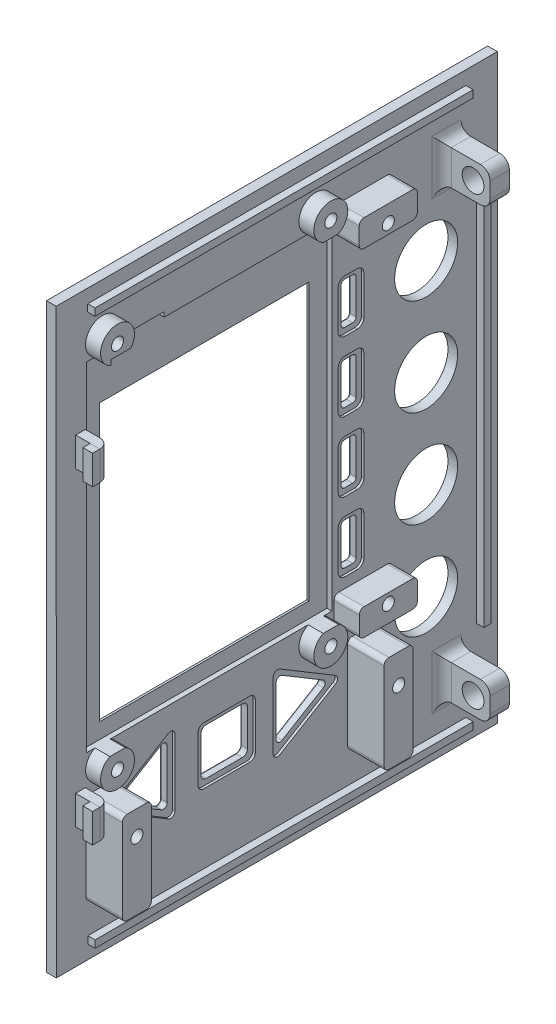
SolidWorks part; units mm, degrees
ref_plane "Front Plane" through (0, 0, 0) normal (0, 0, 1) x (1, 0, 0)
ref_plane "Top Plane" through (0, 0, 0) normal (0, 1, 0) x (1, 0, 0)
ref_plane "Right Plane" through (0, 0, 0) normal (1, 0, 0) x (0, 0, -1)
ref_plane "Plane2" through (-1175.548, -0.0877, 0) normal (-1, -0.0001, 0) x (0, 0, 1)
sketch "Sketch2" plane through (-1175.548, -0.0877, 0) normal (-1, -0.0001, 0) x (0, 0, 1)
  line L0 (-1289.195, -889.282) -> (-1289.195, -789.282) construction
  line L1 (-1204.195, -779.282) -> (-1295.195, -779.282)
  line L2 (-1204.195, -779.282) -> (-1204.195, -899.282)
  line L3 (-1204.195, -899.282) -> (-1295.195, -899.282)
  line L4 (-1295.195, -779.282) -> (-1295.195, -899.282)
  line L5 (-1289.195, -889.282) -> (-1287.685, -889.282) construction
  line L6 (-1289.195, -789.282) -> (-1287.685, -789.282) construction
  circle A0 centre (-1280.5, -869.282) radius 6.5
  circle A1 centre (-1280.5, -849.282) radius 6.5
  circle A2 centre (-1280.5, -829.282) radius 6.5
  circle A3 centre (-1280.5, -809.282) radius 6.5
  ellipse E0 centre (-1280.5, -869.282) end of major axis (-1281.15, -869.2796) minor radius 0.65 construction
  ellipse E1 centre (-1280.5, -849.282) end of major axis (-1281.15, -849.2796) minor radius 0.65 construction
  ellipse E2 centre (-1280.5, -829.282) end of major axis (-1281.15, -829.2796) minor radius 0.65 construction
  ellipse E3 centre (-1280.5, -809.282) end of major axis (-1281.15, -809.2796) minor radius 0.65 construction
  ellipse E4 centre (-1280.5, -869.282) end of major axis (-1281.15, -869.2796) minor radius 0.65
  ellipse E5 centre (-1280.5, -849.282) end of major axis (-1281.15, -849.2796) minor radius 0.65 construction
  ellipse E6 centre (-1280.5, -829.282) end of major axis (-1281.15, -829.2796) minor radius 0.65
  ellipse E7 centre (-1280.5, -809.282) end of major axis (-1281.15, -809.2796) minor radius 0.65
  dimension "D5" = 13
  dimension "D6" = 13
  dimension "D7" = 13
  dimension "D8" = 13
  dimension "D1" = 6
  dimension "D2" = 10
  dimension "D3" = 10
  dimension "D4" = 91
extrude "Boss-Extrude2" add sketch "Sketch2" along normal blind 2 contours L1 L4 L3 L2 A3 A2 A1 A0 region at (-1175.4854, -839.3697, -1248.1207)
sketch "Sketch3" plane through (-1177.548, -0.0879, 0) normal (-1, -0.0001, 0) x (0, 0, 1)
  line L12 (-1214.15, -858.982) -> (-1257.35, -858.982) construction
  line L13 (-1257.35, -858.982) -> (-1257.35, -802.002) construction
  line L14 (-1214.15, -802.002) -> (-1214.15, -858.982) construction
  line L15 (-1257.35, -802.002) -> (-1214.15, -802.002) construction
  line L16 (-1214.15, -858.982) -> (-1257.35, -858.982)
  line L17 (-1257.35, -858.982) -> (-1257.35, -802.002)
  line L18 (-1214.15, -802.002) -> (-1214.15, -858.982)
  line L19 (-1257.35, -802.002) -> (-1214.15, -802.002)
extrude "tft_cutout" cut sketch "Sketch3" against normal through all
sketch "tft_inset_cutout" plane through (-1175.548, -0.0877, 0) normal (1, 0.0001, 0) x (0, 0, -1)
  line L4 (1210.95, -792.861) -> (1210.95, -861.661) construction
  line L5 (1260.55, -792.861) -> (1210.95, -792.861) construction
  line L12 (1260.55, -861.661) -> (1260.55, -792.861) construction
  line L17 (1210.95, -861.661) -> (1260.55, -861.661) construction
  line L18 (1260.55, -861.661) -> (1260.55, -792.861) construction
  line L19 (1210.95, -861.661) -> (1260.55, -861.661) construction
  line L20 (1210.95, -792.861) -> (1210.95, -861.661) construction
  line L21 (1260.55, -792.861) -> (1210.95, -792.861) construction
  line L22 (1261.05, -792.361) -> (1210.45, -792.361)
  line L26 (1212.45, -792.861) -> (1226.45, -792.861)
  line L27 (1212.45, -792.861) -> (1212.45, -791.361)
  line L28 (1212.45, -791.361) -> (1226.45, -791.361)
  line L29 (1226.45, -792.861) -> (1226.45, -791.361)
  line L30 (1210.45, -792.361) -> (1210.45, -862.161)
  line L31 (1210.45, -862.161) -> (1261.05, -862.161)
  line L32 (1261.05, -862.161) -> (1261.05, -792.361)
  line M40 (1257.35, -858.982) -> (1214.15, -858.982)
  line M41 (1214.15, -858.982) -> (1214.15, -802.002)
  line M42 (1214.15, -802.002) -> (1257.35, -802.002)
  line M43 (1257.35, -802.002) -> (1257.35, -858.982)
  dimension "D3" = 1.5
  dimension "D4" = 0.5
  dimension "D1" = 14
  dimension "D2" = 1.5
extrude "Cut-Extrude2" cut sketch "tft_inset_cutout" against normal up to surface (1 mm away) contours L18 | L31 L32 L22 L29 L26 L27 L30 M43 M40 M41 M42 | L26 L29 L22 L27 | L22 L29 L28 L27 region at (-1175.4863, -827.3487, -1260.1879) region at (-1175.4889, -792.6987, -1219.45) region at (-1175.4889, -791.9487, -1219.45)
chamfer "Chamfer2" distance 1 angle 30 4 edges at (-1177.486, -830.5799, -1257.35) (-1177.4839, -859.0699, -1235.75) (-1177.486, -830.5799, -1214.15) (-1177.4882, -802.0899, -1235.75) first distance on face at (-1177.486, -830.5799, -1235.75)
sketch "Sketch6" plane through (-1175.548, -0.0877, 0) normal (1, 0.0001, 0) x (0, 0, -1)
  line L5 (1261.5, -864.9905) -> (1273.5, -864.9905)
  line L6 (1261.5, -864.9905) -> (1261.5, -859.4905)
  line L7 (1261.5, -859.4905) -> (1273.5, -859.4905)
  line L8 (1261.5, -864.9905) -> (1273.5, -864.9905)
  line L9 (1273.5, -864.9905) -> (1273.5, -789.9905)
  line L10 (1273.5, -789.9905) -> (1261.5, -789.9905)
  line L11 (1261.5, -789.9905) -> (1261.5, -864.9905)
  line L12 (1261.5, -864.9905) -> (1273.5, -864.9905) construction
  line L13 (1273.5, -864.9905) -> (1273.5, -789.9905) construction
  line L14 (1273.5, -789.9905) -> (1261.5, -789.9905) construction
  line L15 (1261.5, -789.9905) -> (1261.5, -864.9905) construction
  line L16 (1273.5, -864.9905) -> (1273.5, -859.4905)
  line L17 (1261.5, -789.9905) -> (1273.5, -789.9905)
  line L18 (1261.5, -789.9905) -> (1261.5, -795.4905)
  line L19 (1261.5, -795.4905) -> (1273.5, -795.4905)
  line L20 (1273.5, -789.9905) -> (1273.5, -795.4905)
  circle A0 centre (1267.5, -861.4905) radius 1.25 construction
  circle A1 centre (1267.5, -861.4905) radius 1.25 construction
  circle A2 centre (1267.5, -861.4905) radius 1.25
  circle A3 centre (1267.5, -793.4905) radius 1.25 construction
  circle A4 centre (1267.5, -793.4905) radius 1.25 construction
  circle A5 centre (1267.5, -793.4905) radius 1.25
  dimension "D2" = 2.5
  dimension "D4" = 2.5
  dimension "D3" = 2
  dimension "D5" = 2
extrude "menu_standoffs" add sketch "Sketch6" along normal up to surface (5.203 mm away)
fillet "Fillet1" radius 1 8 edges at (-1172.8871, -795.5781, -1261.5) (-1172.8871, -795.5781, -1273.5) (-1172.8875, -790.0781, -1273.5) (-1172.8875, -790.0781, -1261.5) (-1172.8824, -859.5781, -1273.5) (-1172.8824, -859.5781, -1261.5) (-1172.882, -865.0781, -1261.5) (-1172.882, -865.0781, -1273.5)
sketch "Sketch7" plane through (-1170.345, -0.0874, 0) normal (1, 0.0001, 0) x (0, 0, -1)
  circle A0 centre (1267.5, -861.4905) radius 1.25 construction
  circle A1 centre (1267.5, -793.4905) radius 1.25 construction
  circle A2 centre (1267.5, -861.4905) radius 1.25
  circle A3 centre (1267.5, -793.4905) radius 1.25
extrude "menu_standoff_holes" [suppressed] cut sketch "Sketch7" against normal blind 5 contours A2
sketch "Sketch8" plane through (-1175.548, -0.0877, 0) normal (1, 0.0001, 0) x (0, 0, -1)
  circle A0 centre (1213.75, -865.282) radius 1.55 construction
  circle A1 centre (1257.75, -865.282) radius 1.55 construction
  circle A2 centre (1257.75, -789.202) radius 1.55 construction
  circle A3 centre (1213.75, -789.2023) radius 1.55 construction
  circle A4 centre (1213.75, -865.282) radius 1.55 construction
  circle A5 centre (1257.75, -865.282) radius 1.55 construction
  circle A6 centre (1257.75, -789.202) radius 1.55 construction
  circle A7 centre (1213.75, -789.2023) radius 1.55 construction
  circle A8 centre (1213.75, -789.2023) radius 3.5
  circle A9 centre (1257.75, -789.202) radius 3.5
  circle A10 centre (1257.75, -865.282) radius 3.5
  circle A11 centre (1213.75, -865.282) radius 3.5
  circle A12 centre (1213.75, -789.2023) radius 1.25
  circle A13 centre (1213.75, -865.282) radius 1.25
  circle A14 centre (1257.75, -865.282) radius 1.25
  circle A15 centre (1257.75, -789.202) radius 1.25
  dimension "D2" = 2.5
  dimension "D1" = 7
extrude "TFT_standoffs" add sketch "Sketch8" along normal up to surface (3.09 mm away)
sketch "Sketch9" plane through (-1175.548, -0.0877, 0) normal (1, 0.0001, 0) x (0, 0, -1)
  circle A0 centre (1213.75, -789.2023) radius 1.25 construction
  circle A1 centre (1213.75, -865.282) radius 1.25 construction
  circle A2 centre (1257.75, -865.282) radius 1.25 construction
  circle A3 centre (1257.75, -789.202) radius 1.25 construction
  circle A4 centre (1213.75, -789.2023) radius 1.25
  circle A5 centre (1213.75, -865.282) radius 1.25
  circle A6 centre (1257.75, -865.282) radius 1.25
  circle A7 centre (1257.75, -789.202) radius 1.25
extrude "TFT_standoff_holes" cut sketch "Sketch9" against normal offset from surface (1 mm away) 1 up to face at (-1177.486, -830.5799, -1235.75)
extrude "Cut-Extrude5" cut sketch "Sketch5<3>" along normal through all contours L31 L32 L22 L29 L26 L27 L30 M43 M40 M41 M42 | L22 L29 L28 L27 | L26 L29 L22 L27 region at (-1175.4863, -827.3487, -1260.1879) region at (-1175.4889, -792.6987, -1219.45) region at (-1175.4889, -791.9487, -1219.45)
sketch "Sketch5<3>" plane through (-1175.548, -0.0877, 0) normal (1, 0.0001, 0) x (0, 0, -1) same geometry as "tft_inset_cutout"
sketch "Sketch10" plane through (-1175.548, -0.0877, 0) normal (1, 0.0001, 0) x (0, 0, -1)
  line L0 (1267.2535, -804.997) -> (1267.2535, -812.997) construction
  line L1 (1266.2535, -813.997) -> (1263.7535, -813.997) construction
  line L2 (1262.7535, -812.997) -> (1262.7535, -804.997) construction
  line L3 (1263.7535, -803.997) -> (1266.2535, -803.997) construction
  line L4 (1267.2535, -804.997) -> (1267.2535, -812.997) construction
  line L5 (1266.2535, -813.997) -> (1263.7535, -813.997) construction
  line L6 (1262.7535, -812.997) -> (1262.7535, -804.997) construction
  line L7 (1263.7535, -803.997) -> (1266.2535, -803.997) construction
  line L8 (1267.6535, -804.997) -> (1267.6535, -812.997)
  line L9 (1266.2535, -814.397) -> (1263.7535, -814.397)
  line L10 (1262.3535, -812.997) -> (1262.3535, -804.997)
  line L11 (1263.7535, -803.597) -> (1266.2535, -803.597)
  line L12 (1267.6535, -819.327) -> (1267.6535, -827.327)
  line L13 (1266.2535, -828.727) -> (1263.7535, -828.727)
  line L14 (1262.3535, -827.327) -> (1262.3535, -819.327)
  line L15 (1263.7535, -817.927) -> (1266.2535, -817.927)
  line L16 (1267.2535, -819.327) -> (1267.2535, -827.327) construction
  line L17 (1266.2535, -828.327) -> (1263.7535, -828.327) construction
  line L18 (1262.7535, -827.327) -> (1262.7535, -819.327) construction
  line L19 (1263.7535, -818.327) -> (1266.2535, -818.327) construction
  line L20 (1267.6535, -833.657) -> (1267.6535, -841.657)
  line L21 (1266.2535, -843.057) -> (1263.7535, -843.057)
  line L22 (1262.3535, -841.657) -> (1262.3535, -833.657)
  line L23 (1263.7535, -832.257) -> (1266.2535, -832.257)
  line L24 (1267.2535, -833.657) -> (1267.2535, -841.657) construction
  line L25 (1266.2535, -842.657) -> (1263.7535, -842.657) construction
  line L26 (1262.7535, -841.657) -> (1262.7535, -833.657) construction
  line L27 (1263.7535, -832.657) -> (1266.2535, -832.657) construction
  line L28 (1267.6535, -847.987) -> (1267.6535, -855.987)
  line L29 (1266.2535, -857.387) -> (1263.7535, -857.387)
  line L30 (1262.3535, -855.987) -> (1262.3535, -847.987)
  line L31 (1263.7535, -846.587) -> (1266.2535, -846.587)
  line L32 (1267.2535, -847.987) -> (1267.2535, -855.987) construction
  line L33 (1266.2535, -856.987) -> (1263.7535, -856.987) construction
  line L34 (1262.7535, -855.987) -> (1262.7535, -847.987) construction
  line L35 (1263.7535, -846.987) -> (1266.2535, -846.987) construction
  arc A0 (1267.2535, -804.997) -> (1266.2535, -803.997) centre (1266.2535, -804.997) ccw construction
  arc A1 (1266.2535, -813.997) -> (1267.2535, -812.997) centre (1266.2535, -812.997) ccw construction
  arc A2 (1262.7535, -812.997) -> (1263.7535, -813.997) centre (1263.7535, -812.997) ccw construction
  arc A3 (1263.7535, -803.997) -> (1262.7535, -804.997) centre (1263.7535, -804.997) ccw construction
  arc A4 (1267.2535, -804.997) -> (1266.2535, -803.997) centre (1266.2535, -804.997) ccw construction
  arc A5 (1266.2535, -813.997) -> (1267.2535, -812.997) centre (1266.2535, -812.997) ccw construction
  arc A6 (1262.7535, -812.997) -> (1263.7535, -813.997) centre (1263.7535, -812.997) ccw construction
  arc A7 (1263.7535, -803.997) -> (1262.7535, -804.997) centre (1263.7535, -804.997) ccw construction
  arc A8 (1266.2535, -814.397) -> (1267.6535, -812.997) centre (1266.2535, -812.997) ccw
  arc A9 (1262.3535, -812.997) -> (1263.7535, -814.397) centre (1263.7535, -812.997) ccw
  arc A10 (1263.7535, -803.597) -> (1262.3535, -804.997) centre (1263.7535, -804.997) ccw
  arc A11 (1267.6535, -804.997) -> (1266.2535, -803.597) centre (1266.2535, -804.997) ccw
  arc A12 (1266.2535, -828.727) -> (1267.6535, -827.327) centre (1266.2535, -827.327) ccw
  arc A13 (1262.3535, -827.327) -> (1263.7535, -828.727) centre (1263.7535, -827.327) ccw
  arc A14 (1263.7535, -817.927) -> (1262.3535, -819.327) centre (1263.7535, -819.327) ccw
  arc A15 (1267.6535, -819.327) -> (1266.2535, -817.927) centre (1266.2535, -819.327) ccw
  arc A16 (1267.2535, -819.327) -> (1266.2535, -818.327) centre (1266.2535, -819.327) ccw construction
  arc A17 (1266.2535, -828.327) -> (1267.2535, -827.327) centre (1266.2535, -827.327) ccw construction
  arc A18 (1262.7535, -827.327) -> (1263.7535, -828.327) centre (1263.7535, -827.327) ccw construction
  arc A19 (1263.7535, -818.327) -> (1262.7535, -819.327) centre (1263.7535, -819.327) ccw construction
  arc A20 (1266.2535, -843.057) -> (1267.6535, -841.657) centre (1266.2535, -841.657) ccw
  arc A21 (1262.3535, -841.657) -> (1263.7535, -843.057) centre (1263.7535, -841.657) ccw
  arc A22 (1263.7535, -832.257) -> (1262.3535, -833.657) centre (1263.7535, -833.657) ccw
  arc A23 (1267.6535, -833.657) -> (1266.2535, -832.257) centre (1266.2535, -833.657) ccw
  arc A24 (1267.2535, -833.657) -> (1266.2535, -832.657) centre (1266.2535, -833.657) ccw construction
  arc A25 (1266.2535, -842.657) -> (1267.2535, -841.657) centre (1266.2535, -841.657) ccw construction
  arc A26 (1262.7535, -841.657) -> (1263.7535, -842.657) centre (1263.7535, -841.657) ccw construction
  arc A27 (1263.7535, -832.657) -> (1262.7535, -833.657) centre (1263.7535, -833.657) ccw construction
  arc A28 (1266.2535, -857.387) -> (1267.6535, -855.987) centre (1266.2535, -855.987) ccw
  arc A29 (1262.3535, -855.987) -> (1263.7535, -857.387) centre (1263.7535, -855.987) ccw
  arc A30 (1263.7535, -846.587) -> (1262.3535, -847.987) centre (1263.7535, -847.987) ccw
  arc A31 (1267.6535, -847.987) -> (1266.2535, -846.587) centre (1266.2535, -847.987) ccw
  arc A32 (1267.2535, -847.987) -> (1266.2535, -846.987) centre (1266.2535, -847.987) ccw construction
  arc A33 (1266.2535, -856.987) -> (1267.2535, -855.987) centre (1266.2535, -855.987) ccw construction
  arc A34 (1262.7535, -855.987) -> (1263.7535, -856.987) centre (1263.7535, -855.987) ccw construction
  arc A35 (1263.7535, -846.987) -> (1262.7535, -847.987) centre (1263.7535, -847.987) ccw construction
  dimension "D1" = 0.4
  dimension "D2" = 4
extrude "menu_panel_inset" cut sketch "Sketch10" against normal offset from surface 1.5 and the other way through all up to face at (-1177.486, -830.5799, -1235.75)
sketch "Sketch11" plane through (-1177.548, -0.0879, 0) normal (-1, -0.0001, 0) x (0, 0, 1)
  line L0 (-1265.8535, -812.997) -> (-1264.1535, -812.997) construction
  line L1 (-1266.2535, -805.397) -> (-1266.2535, -812.597) construction
  line L2 (-1265.8535, -804.997) -> (-1264.1535, -804.997) construction
  line L3 (-1263.7535, -805.397) -> (-1263.7535, -812.597) construction
  line L4 (-1265.8535, -812.997) -> (-1264.1535, -812.997) construction
  line L5 (-1266.2535, -805.397) -> (-1266.2535, -812.597) construction
  line L6 (-1265.8535, -804.997) -> (-1264.1535, -804.997) construction
  line L7 (-1263.7535, -805.397) -> (-1263.7535, -812.597) construction
  line L8 (-1263.4535, -805.397) -> (-1263.4535, -812.597)
  line L9 (-1265.8535, -813.297) -> (-1264.1535, -813.297)
  line L10 (-1266.5535, -805.397) -> (-1266.5535, -812.597)
  line L11 (-1265.8535, -804.697) -> (-1264.1535, -804.697)
  line L12 (-1263.4535, -819.727) -> (-1263.4535, -826.927)
  line L13 (-1265.8535, -827.627) -> (-1264.1535, -827.627)
  line L14 (-1266.5535, -819.727) -> (-1266.5535, -826.927)
  line L15 (-1265.8535, -819.027) -> (-1264.1535, -819.027)
  line L16 (-1265.8535, -827.327) -> (-1264.1535, -827.327) construction
  line L17 (-1266.2535, -819.727) -> (-1266.2535, -826.927) construction
  line L18 (-1265.8535, -819.327) -> (-1264.1535, -819.327) construction
  line L19 (-1263.7535, -819.727) -> (-1263.7535, -826.927) construction
  line L20 (-1263.4535, -834.057) -> (-1263.4535, -841.257)
  line L21 (-1265.8535, -841.957) -> (-1264.1535, -841.957)
  line L22 (-1266.5535, -834.057) -> (-1266.5535, -841.257)
  line L23 (-1265.8535, -833.357) -> (-1264.1535, -833.357)
  line L24 (-1265.8535, -841.657) -> (-1264.1535, -841.657) construction
  line L25 (-1266.2535, -834.057) -> (-1266.2535, -841.257) construction
  line L26 (-1265.8535, -833.657) -> (-1264.1535, -833.657) construction
  line L27 (-1263.7535, -834.057) -> (-1263.7535, -841.257) construction
  line L28 (-1263.4535, -848.387) -> (-1263.4535, -855.587)
  line L29 (-1265.8535, -856.287) -> (-1264.1535, -856.287)
  line L30 (-1266.5535, -848.387) -> (-1266.5535, -855.587)
  line L31 (-1265.8535, -847.687) -> (-1264.1535, -847.687)
  line L32 (-1265.8535, -855.987) -> (-1264.1535, -855.987) construction
  line L33 (-1266.2535, -848.387) -> (-1266.2535, -855.587) construction
  line L34 (-1265.8535, -847.987) -> (-1264.1535, -847.987) construction
  line L35 (-1263.7535, -848.387) -> (-1263.7535, -855.587) construction
  arc A0 (-1264.1535, -812.997) -> (-1263.7535, -812.597) centre (-1264.1535, -812.597) ccw construction
  arc A1 (-1266.2535, -812.597) -> (-1265.8535, -812.997) centre (-1265.8535, -812.597) ccw construction
  arc A2 (-1265.8535, -804.997) -> (-1266.2535, -805.397) centre (-1265.8535, -805.397) ccw construction
  arc A3 (-1263.7535, -805.397) -> (-1264.1535, -804.997) centre (-1264.1535, -805.397) ccw construction
  arc A4 (-1264.1535, -812.997) -> (-1263.7535, -812.597) centre (-1264.1535, -812.597) ccw construction
  arc A5 (-1266.2535, -812.597) -> (-1265.8535, -812.997) centre (-1265.8535, -812.597) ccw construction
  arc A6 (-1265.8535, -804.997) -> (-1266.2535, -805.397) centre (-1265.8535, -805.397) ccw construction
  arc A7 (-1263.7535, -805.397) -> (-1264.1535, -804.997) centre (-1264.1535, -805.397) ccw construction
  arc A8 (-1264.1535, -813.297) -> (-1263.4535, -812.597) centre (-1264.1535, -812.597) ccw
  arc A9 (-1266.5535, -812.597) -> (-1265.8535, -813.297) centre (-1265.8535, -812.597) ccw
  arc A10 (-1265.8535, -804.697) -> (-1266.5535, -805.397) centre (-1265.8535, -805.397) ccw
  arc A11 (-1263.4535, -805.397) -> (-1264.1535, -804.697) centre (-1264.1535, -805.397) ccw
  arc A12 (-1264.1535, -827.627) -> (-1263.4535, -826.927) centre (-1264.1535, -826.927) ccw
  arc A13 (-1266.5535, -826.927) -> (-1265.8535, -827.627) centre (-1265.8535, -826.927) ccw
  arc A14 (-1265.8535, -819.027) -> (-1266.5535, -819.727) centre (-1265.8535, -819.727) ccw
  arc A15 (-1263.4535, -819.727) -> (-1264.1535, -819.027) centre (-1264.1535, -819.727) ccw
  arc A16 (-1264.1535, -827.327) -> (-1263.7535, -826.927) centre (-1264.1535, -826.927) ccw construction
  arc A17 (-1266.2535, -826.927) -> (-1265.8535, -827.327) centre (-1265.8535, -826.927) ccw construction
  arc A18 (-1265.8535, -819.327) -> (-1266.2535, -819.727) centre (-1265.8535, -819.727) ccw construction
  arc A19 (-1263.7535, -819.727) -> (-1264.1535, -819.327) centre (-1264.1535, -819.727) ccw construction
  arc A20 (-1264.1535, -841.957) -> (-1263.4535, -841.257) centre (-1264.1535, -841.257) ccw
  arc A21 (-1266.5535, -841.257) -> (-1265.8535, -841.957) centre (-1265.8535, -841.257) ccw
  arc A22 (-1265.8535, -833.357) -> (-1266.5535, -834.057) centre (-1265.8535, -834.057) ccw
  arc A23 (-1263.4535, -834.057) -> (-1264.1535, -833.357) centre (-1264.1535, -834.057) ccw
  arc A24 (-1264.1535, -841.657) -> (-1263.7535, -841.257) centre (-1264.1535, -841.257) ccw construction
  arc A25 (-1266.2535, -841.257) -> (-1265.8535, -841.657) centre (-1265.8535, -841.257) ccw construction
  arc A26 (-1265.8535, -833.657) -> (-1266.2535, -834.057) centre (-1265.8535, -834.057) ccw construction
  arc A27 (-1263.7535, -834.057) -> (-1264.1535, -833.657) centre (-1264.1535, -834.057) ccw construction
  arc A28 (-1264.1535, -856.287) -> (-1263.4535, -855.587) centre (-1264.1535, -855.587) ccw
  arc A29 (-1266.5535, -855.587) -> (-1265.8535, -856.287) centre (-1265.8535, -855.587) ccw
  arc A30 (-1265.8535, -847.687) -> (-1266.5535, -848.387) centre (-1265.8535, -848.387) ccw
  arc A31 (-1263.4535, -848.387) -> (-1264.1535, -847.687) centre (-1264.1535, -848.387) ccw
  arc A32 (-1264.1535, -855.987) -> (-1263.7535, -855.587) centre (-1264.1535, -855.587) ccw construction
  arc A33 (-1266.2535, -855.587) -> (-1265.8535, -855.987) centre (-1265.8535, -855.587) ccw construction
  arc A34 (-1265.8535, -847.987) -> (-1266.2535, -848.387) centre (-1265.8535, -848.387) ccw construction
  arc A35 (-1263.7535, -848.387) -> (-1264.1535, -847.987) centre (-1264.1535, -848.387) ccw construction
  dimension "D1" = 0.3
  dimension "D2" = 4
extrude "menu_panel_cutout" cut sketch "Sketch11" against normal through all
fillet "Fillet2" radius 0.25 32 edges at (-1177.4876, -809.0849, -1263.4535) (-1177.4873, -813.1798, -1263.6586) (-1177.4873, -813.3849, -1265.0035) (-1177.4873, -813.1798, -1266.3485) (-1177.4876, -809.0849, -1266.5535) (-1177.4879, -804.9899, -1266.3485) (-1177.488, -804.7849, -1265.0035) (-1177.4862, -827.7149, -1265.0035) (-1177.4863, -827.5098, -1266.3485) (-1177.4866, -823.4149, -1266.5535) (-1177.4869, -819.3199, -1266.3485) (-1177.4869, -819.1149, -1265.0035) (-1177.4869, -819.3199, -1263.6586) (-1177.4866, -823.4149, -1263.4535) (-1177.4852, -842.0449, -1265.0035) (-1177.4852, -841.8398, -1266.3485) (-1177.4855, -837.7449, -1266.5535) (-1177.4858, -833.6499, -1266.3485) (-1177.4858, -833.4449, -1265.0035) (-1177.4858, -833.6499, -1263.6586) (-1177.4855, -837.7449, -1263.4535) (-1177.4844, -852.0749, -1263.4535) (-1177.4841, -856.1698, -1263.6586) (-1177.4841, -856.3749, -1265.0035) (-1177.4841, -856.1698, -1266.3485) (-1177.4844, -852.0749, -1266.5535) (-1177.4847, -847.9799, -1266.3485) (-1177.4847, -847.7749, -1265.0035) (-1177.4879, -804.9899, -1263.6586) (-1177.4863, -827.5098, -1263.6586) (-1177.4852, -841.8398, -1263.6586) (-1177.4847, -847.9799, -1263.6586)
sketch "Sketch12" plane through (-1175.548, -0.0877, 0) normal (1, 0.0001, 0) x (0, 0, -1)
  line L0 (1270.2797, -888.782) -> (1210.2797, -888.782) construction
  line L1 (1270.2797, -868.782) -> (1264.2797, -868.782)
  line L2 (1270.2797, -868.782) -> (1270.2797, -888.782)
  line L3 (1270.2797, -888.782) -> (1264.2797, -888.782)
  line L4 (1264.2797, -868.782) -> (1264.2797, -888.782)
  line L6 (1210.2797, -888.782) -> (1216.2797, -888.782)
  line L7 (1210.2797, -888.782) -> (1210.2797, -869.782)
  line L8 (1210.2797, -869.782) -> (1216.2797, -869.782)
  line L9 (1216.2797, -888.782) -> (1216.2797, -869.782)
  line L10 (1210.2797, -868.782) -> (1270.2797, -868.782) construction
  circle A0 centre (1267.2797, -874.782) radius 1.25
  circle A1 centre (1213.2797, -874.782) radius 1.25
  dimension "D1" = 6
  dimension "D2" = 2.5
  dimension "D4" = 2.5
  dimension "D3" = 6
  dimension "D5" = 1
extrude "selector_standoffs" add sketch "Sketch12" along normal up to surface (7.55 mm away) contours L6 L9 L8 L7 A1 | L1 L4 L3 L2 A0 region at (-1175.4824, -879.0403, -1267.2797) region at (-1175.4824, -879.5722, -1213.2797)
fillet "Fillet3" radius 1 8 edges at (-1171.7067, -888.8694, -1270.2797) (-1171.7082, -868.8694, -1270.2797) (-1171.7082, -868.8694, -1264.2797) (-1171.7067, -888.8694, -1264.2797) (-1171.7067, -888.8694, -1216.2797) (-1171.7067, -888.8694, -1210.2797) (-1171.7081, -869.8694, -1210.2797) (-1171.7081, -869.8694, -1216.2797)
sketch "Sketch13" plane through (-1175.548, -0.0877, 0) normal (1, 0.0001, 0) x (0, 0, -1)
  line L0 (1218.0014, -875.2178) -> (1226.5296, -880.3347) construction
  line L1 (1227.2868, -879.906) -> (1227.2868, -869.6722) construction
  line L2 (1226.5296, -869.2434) -> (1218.0014, -874.3603) construction
  line L3 (1234.85, -871.0391) -> (1234.85, -878.5391) construction
  line L4 (1235.6, -879.2891) -> (1243.1, -879.2891) construction
  line L5 (1243.1, -870.2891) -> (1235.6, -870.2891) construction
  line L6 (1243.85, -878.5391) -> (1243.85, -871.0391) construction
  line L7 (1259.6354, -874.3603) -> (1251.1072, -869.2434) construction
  line L8 (1250.35, -869.6722) -> (1250.35, -879.906) construction
  line L9 (1251.1072, -880.3347) -> (1259.6354, -875.2178) construction
  line L10 (1218.0014, -875.2178) -> (1226.5296, -880.3347) construction
  line L11 (1227.2868, -879.906) -> (1227.2868, -869.6722) construction
  line L12 (1226.5296, -869.2434) -> (1218.0014, -874.3603) construction
  line L13 (1234.85, -871.0391) -> (1234.85, -878.5391) construction
  line L14 (1235.6, -879.2891) -> (1243.1, -879.2891) construction
  line L15 (1243.1, -870.2891) -> (1235.6, -870.2891) construction
  line L16 (1243.85, -878.5391) -> (1243.85, -871.0391) construction
  line L17 (1259.6354, -874.3603) -> (1251.1072, -869.2434) construction
  line L18 (1250.35, -869.6722) -> (1250.35, -879.906) construction
  line L19 (1251.1072, -880.3347) -> (1259.6354, -875.2178) construction
  line L20 (1217.847, -875.4751) -> (1226.3752, -880.592)
  line L21 (1227.5868, -879.906) -> (1227.5868, -869.6722)
  line L22 (1226.3752, -868.9862) -> (1217.847, -874.1031)
  line L23 (1234.55, -871.0391) -> (1234.55, -878.5391)
  line L24 (1235.6, -879.5891) -> (1243.1, -879.5891)
  line L25 (1244.15, -878.5391) -> (1244.15, -871.0391)
  line L26 (1243.1, -869.9891) -> (1235.6, -869.9891)
  line L27 (1259.7898, -874.1031) -> (1251.2616, -868.9862)
  line L28 (1250.05, -869.6722) -> (1250.05, -879.906)
  line L29 (1251.2616, -880.592) -> (1259.7898, -875.4751)
  arc A0 (1218.0014, -874.3603) -> (1218.0014, -875.2178) centre (1218.2586, -874.7891) ccw construction
  arc A1 (1226.5296, -880.3347) -> (1227.2868, -879.906) centre (1226.7868, -879.906) ccw construction
  arc A2 (1227.2868, -869.6722) -> (1226.5296, -869.2434) centre (1226.7868, -869.6722) ccw construction
  arc A3 (1235.6, -870.2891) -> (1234.85, -871.0391) centre (1235.6, -871.0391) ccw construction
  arc A4 (1234.85, -878.5391) -> (1235.6, -879.2891) centre (1235.6, -878.5391) ccw construction
  arc A5 (1243.1, -879.2891) -> (1243.85, -878.5391) centre (1243.1, -878.5391) ccw construction
  arc A6 (1243.85, -871.0391) -> (1243.1, -870.2891) centre (1243.1, -871.0391) ccw construction
  arc A7 (1259.6354, -875.2178) -> (1259.6354, -874.3603) centre (1259.3782, -874.7891) ccw construction
  arc A8 (1251.1072, -869.2434) -> (1250.35, -869.6722) centre (1250.85, -869.6722) ccw construction
  arc A9 (1250.35, -879.906) -> (1251.1072, -880.3347) centre (1250.85, -879.906) ccw construction
  arc A10 (1218.0014, -874.3603) -> (1218.0014, -875.2178) centre (1218.2586, -874.7891) ccw construction
  arc A11 (1226.5296, -880.3347) -> (1227.2868, -879.906) centre (1226.7868, -879.906) ccw construction
  arc A12 (1227.2868, -869.6722) -> (1226.5296, -869.2434) centre (1226.7868, -869.6722) ccw construction
  arc A13 (1235.6, -870.2891) -> (1234.85, -871.0391) centre (1235.6, -871.0391) ccw construction
  arc A14 (1234.85, -878.5391) -> (1235.6, -879.2891) centre (1235.6, -878.5391) ccw construction
  arc A15 (1243.1, -879.2891) -> (1243.85, -878.5391) centre (1243.1, -878.5391) ccw construction
  arc A16 (1243.85, -871.0391) -> (1243.1, -870.2891) centre (1243.1, -871.0391) ccw construction
  arc A17 (1259.6354, -875.2178) -> (1259.6354, -874.3603) centre (1259.3782, -874.7891) ccw construction
  arc A18 (1251.1072, -869.2434) -> (1250.35, -869.6722) centre (1250.85, -869.6722) ccw construction
  arc A19 (1250.35, -879.906) -> (1251.1072, -880.3347) centre (1250.85, -879.906) ccw construction
  arc A20 (1226.3752, -880.592) -> (1227.5868, -879.906) centre (1226.7868, -879.906) ccw
  arc A21 (1227.5868, -869.6722) -> (1226.3752, -868.9862) centre (1226.7868, -869.6722) ccw
  arc A22 (1217.847, -874.1031) -> (1217.847, -875.4751) centre (1218.2586, -874.7891) ccw
  arc A23 (1234.55, -878.5391) -> (1235.6, -879.5891) centre (1235.6, -878.5391) ccw
  arc A24 (1243.1, -879.5891) -> (1244.15, -878.5391) centre (1243.1, -878.5391) ccw
  arc A25 (1244.15, -871.0391) -> (1243.1, -869.9891) centre (1243.1, -871.0391) ccw
  arc A26 (1235.6, -869.9891) -> (1234.55, -871.0391) centre (1235.6, -871.0391) ccw
  arc A27 (1251.2616, -868.9862) -> (1250.05, -869.6722) centre (1250.85, -869.6722) ccw
  arc A28 (1250.05, -879.906) -> (1251.2616, -880.592) centre (1250.85, -879.906) ccw
  arc A29 (1259.7898, -875.4751) -> (1259.7898, -874.1031) centre (1259.3782, -874.7891) ccw
  dimension "D1" = 0.3
  dimension "D2" = 0.3
  dimension "D3" = 0.3
extrude "selector_cutout" cut sketch "Sketch13" against normal through all
fillet "Fillet4" radius 0.25 20 edges at (-1177.4824, -879.677, -1239.35) (-1177.4824, -879.3694, -1234.8575) (-1177.4827, -874.877, -1234.55) (-1177.4831, -870.3845, -1234.8575) (-1177.4831, -870.077, -1239.35) (-1177.4831, -870.3845, -1243.8424) (-1177.4827, -874.877, -1244.15) (-1177.4832, -869.0639, -1250.4558) (-1177.483, -871.6325, -1255.5257) (-1177.4827, -874.877, -1260.1782) (-1177.4825, -878.1214, -1255.5257) (-1177.4823, -880.69, -1250.4558) (-1177.4824, -879.3694, -1243.8424) (-1177.4827, -874.877, -1250.05) (-1177.4825, -878.1214, -1222.1111) (-1177.4827, -874.877, -1217.4586) (-1177.483, -871.6325, -1222.1111) (-1177.4832, -869.0639, -1227.181) (-1177.4827, -874.877, -1227.5868) (-1177.4823, -880.69, -1227.181)
sketch "Sketch17" plane through (-1175.548, -0.0877, 0) normal (1, 0.0001, 0) x (0, 0, -1)
  line L18 (1220.3082, -871.8101) -> (1216.0577, -874.3603) construction
  line L19 (1216.0577, -875.2178) -> (1220.3082, -877.7681) construction
  line L20 (1220.1868, -877.5537) -> (1220.1868, -872.0244) construction
  line L21 (1228.2868, -881.6722) -> (1228.2868, -867.906) construction
  line L22 (1227.5296, -867.4772) -> (1220.4505, -871.7247) construction
  line L23 (1220.5791, -871.6891) -> (1226.1368, -871.6891) construction
  line L24 (1226.3868, -871.9391) -> (1226.3868, -877.6391) construction
  line L25 (1226.1368, -877.8891) -> (1220.5791, -877.8891) construction
  line L26 (1220.4505, -877.8535) -> (1227.5296, -882.1009) construction
  line L27 (1220.3082, -871.8101) -> (1216.0577, -874.3603) construction
  line L28 (1216.0577, -875.2178) -> (1220.3082, -877.7681) construction
  line L29 (1220.1868, -877.5537) -> (1220.1868, -872.0244) construction
  line L30 (1228.2868, -881.6722) -> (1228.2868, -867.906) construction
  line L31 (1257.3286, -877.7681) -> (1261.5791, -875.2178) construction
  line L32 (1261.5791, -874.3603) -> (1257.3286, -871.8101) construction
  line L33 (1257.45, -872.0244) -> (1257.45, -877.5537) construction
  line L34 (1249.35, -867.906) -> (1249.35, -881.6722) construction
  line L35 (1250.1072, -882.1009) -> (1257.1863, -877.8535) construction
  line L36 (1257.0577, -877.8891) -> (1251.5, -877.8891) construction
  line L37 (1251.25, -877.6391) -> (1251.25, -871.9391) construction
  line L38 (1251.5, -871.6891) -> (1257.0577, -871.6891) construction
  line L39 (1257.1863, -871.7247) -> (1250.1072, -867.4772) construction
  line L40 (1233.85, -870.0391) -> (1233.85, -879.5391) construction
  line L41 (1234.6, -880.2891) -> (1244.1, -880.2891) construction
  line L42 (1244.85, -879.5391) -> (1244.85, -870.0391) construction
  line L43 (1244.1, -869.2891) -> (1234.6, -869.2891) construction
  line L44 (1257.3286, -877.7681) -> (1261.5791, -875.2178) construction
  line L45 (1261.5791, -874.3603) -> (1257.3286, -871.8101) construction
  line L46 (1257.45, -872.0244) -> (1257.45, -877.5537) construction
  line L47 (1249.35, -867.906) -> (1249.35, -881.6722) construction
  line L48 (1250.1072, -882.1009) -> (1257.1863, -877.8535) construction
  line L49 (1257.0577, -877.8891) -> (1251.5, -877.8891) construction
  line L50 (1251.25, -877.6391) -> (1251.25, -871.9391) construction
  line L51 (1251.5, -871.6891) -> (1257.0577, -871.6891) construction
  line L52 (1257.1863, -871.7247) -> (1250.1072, -867.4772) construction
  line L53 (1233.85, -870.0391) -> (1233.85, -879.5391) construction
  line L54 (1234.6, -880.2891) -> (1244.1, -880.2891) construction
  line L55 (1244.85, -879.5391) -> (1244.85, -870.0391) construction
  line L56 (1244.1, -869.2891) -> (1234.6, -869.2891) construction
  line L57 (1257.1863, -877.8535) -> (1257.3286, -877.7681)
  line L58 (1257.3286, -871.8101) -> (1257.1863, -871.7247)
  line L59 (1227.5296, -867.4772) -> (1220.4505, -871.7247) construction
  line L60 (1220.5791, -871.6891) -> (1226.1368, -871.6891) construction
  line L61 (1226.3868, -871.9391) -> (1226.3868, -877.6391) construction
  line L62 (1226.1368, -877.8891) -> (1220.5791, -877.8891) construction
  line L63 (1220.4505, -877.8535) -> (1227.5296, -882.1009) construction
  line L64 (1220.3082, -871.8101) -> (1220.4505, -871.7247)
  line L65 (1220.4505, -877.8535) -> (1220.3082, -877.7681)
  line L66 (1257.3921, -878.1965) -> (1257.5344, -878.1111)
  line L67 (1257.5344, -871.4671) -> (1257.3921, -871.3817)
  line L68 (1220.514, -872.1531) -> (1220.6563, -872.0677)
  line L69 (1220.6563, -877.5105) -> (1220.514, -877.4251)
  line L70 (1220.1024, -871.4671) -> (1215.8519, -874.0173)
  line L71 (1215.8519, -875.5608) -> (1220.1024, -878.1111)
  line L72 (1220.5868, -877.4811) -> (1220.5868, -872.0971)
  line L73 (1220.2447, -878.1965) -> (1227.3238, -882.4439)
  line L74 (1228.6868, -881.6722) -> (1228.6868, -867.906)
  line L75 (1227.3238, -867.1342) -> (1220.2447, -871.3817)
  line L76 (1257.5344, -878.1111) -> (1261.7849, -875.5608)
  line L77 (1261.7849, -874.0173) -> (1257.5344, -871.4671)
  line L78 (1257.05, -872.0971) -> (1257.05, -877.4811)
  line L79 (1257.3921, -871.3817) -> (1250.313, -867.1342)
  line L80 (1248.95, -867.906) -> (1248.95, -881.6722)
  line L81 (1250.313, -882.4439) -> (1257.3921, -878.1965)
  line L82 (1257.0213, -877.4891) -> (1251.65, -877.4891)
  line L83 (1251.65, -877.4891) -> (1251.65, -872.0891)
  line L84 (1251.65, -872.0891) -> (1257.0213, -872.0891)
  line L85 (1233.45, -870.0391) -> (1233.45, -879.5391)
  line L86 (1234.6, -880.6891) -> (1244.1, -880.6891)
  line L87 (1245.25, -879.5391) -> (1245.25, -870.0391)
  line L88 (1244.1, -868.8891) -> (1234.6, -868.8891)
  line L89 (1220.6155, -872.0891) -> (1225.9868, -872.0891)
  line L90 (1225.9868, -872.0891) -> (1225.9868, -877.4891)
  line L91 (1225.9868, -877.4891) -> (1220.6155, -877.4891)
  line L92 (1220.1024, -878.1111) -> (1220.2447, -878.1965)
  line L93 (1220.2447, -871.3817) -> (1220.1024, -871.4671)
  arc A18 (1216.0577, -874.3603) -> (1216.0577, -875.2178) centre (1216.315, -874.7891) ccw construction
  arc A19 (1220.1868, -877.5537) -> (1220.3082, -877.7681) centre (1220.4368, -877.5537) ccw construction
  arc A20 (1220.3082, -871.8101) -> (1220.1868, -872.0244) centre (1220.4368, -872.0244) ccw construction
  arc A21 (1228.2868, -867.906) -> (1227.5296, -867.4772) centre (1227.7868, -867.906) ccw construction
  arc A22 (1220.5791, -871.6891) -> (1220.4505, -871.7247) centre (1220.5791, -871.9391) ccw construction
  arc A23 (1226.3868, -871.9391) -> (1226.1368, -871.6891) centre (1226.1368, -871.9391) ccw construction
  arc A24 (1226.1368, -877.8891) -> (1226.3868, -877.6391) centre (1226.1368, -877.6391) ccw construction
  arc A25 (1220.4505, -877.8535) -> (1220.5791, -877.8891) centre (1220.5791, -877.6391) ccw construction
  arc A26 (1227.5296, -882.1009) -> (1228.2868, -881.6722) centre (1227.7868, -881.6722) ccw construction
  arc A27 (1261.5791, -875.2178) -> (1261.5791, -874.3603) centre (1261.3218, -874.7891) ccw construction
  arc A28 (1257.45, -872.0244) -> (1257.3286, -871.8101) centre (1257.2, -872.0244) ccw construction
  arc A29 (1257.3286, -877.7681) -> (1257.45, -877.5537) centre (1257.2, -877.5537) ccw construction
  arc A30 (1249.35, -881.6722) -> (1250.1072, -882.1009) centre (1249.85, -881.6722) ccw construction
  arc A31 (1257.0577, -877.8891) -> (1257.1863, -877.8535) centre (1257.0577, -877.6391) ccw construction
  arc A32 (1251.25, -877.6391) -> (1251.5, -877.8891) centre (1251.5, -877.6391) ccw construction
  arc A33 (1251.5, -871.6891) -> (1251.25, -871.9391) centre (1251.5, -871.9391) ccw construction
  arc A34 (1257.1863, -871.7247) -> (1257.0577, -871.6891) centre (1257.0577, -871.9391) ccw construction
  arc A35 (1250.1072, -867.4772) -> (1249.35, -867.906) centre (1249.85, -867.906) ccw construction
  arc A36 (1233.85, -879.5391) -> (1234.6, -880.2891) centre (1234.6, -879.5391) ccw construction
  arc A37 (1244.1, -880.2891) -> (1244.85, -879.5391) centre (1244.1, -879.5391) ccw construction
  arc A38 (1244.85, -870.0391) -> (1244.1, -869.2891) centre (1244.1, -870.0391) ccw construction
  arc A39 (1234.6, -869.2891) -> (1233.85, -870.0391) centre (1234.6, -870.0391) ccw construction
  arc A40 (1261.5791, -875.2178) -> (1261.5791, -874.3603) centre (1261.3218, -874.7891) ccw construction
  arc A41 (1257.45, -872.0244) -> (1257.3286, -871.8101) centre (1257.2, -872.0244) ccw construction
  arc A42 (1257.3286, -877.7681) -> (1257.45, -877.5537) centre (1257.2, -877.5537) ccw construction
  arc A43 (1249.35, -881.6722) -> (1250.1072, -882.1009) centre (1249.85, -881.6722) ccw construction
  arc A44 (1257.0577, -877.8891) -> (1257.1863, -877.8535) centre (1257.0577, -877.6391) ccw construction
  arc A45 (1251.25, -877.6391) -> (1251.5, -877.8891) centre (1251.5, -877.6391) ccw construction
  arc A46 (1251.5, -871.6891) -> (1251.25, -871.9391) centre (1251.5, -871.9391) ccw construction
  arc A47 (1257.1863, -871.7247) -> (1257.0577, -871.6891) centre (1257.0577, -871.9391) ccw construction
  arc A48 (1250.1072, -867.4772) -> (1249.35, -867.906) centre (1249.85, -867.906) ccw construction
  arc A49 (1233.85, -879.5391) -> (1234.6, -880.2891) centre (1234.6, -879.5391) ccw construction
  arc A50 (1244.1, -880.2891) -> (1244.85, -879.5391) centre (1244.1, -879.5391) ccw construction
  arc A51 (1244.85, -870.0391) -> (1244.1, -869.2891) centre (1244.1, -870.0391) ccw construction
  arc A52 (1234.6, -869.2891) -> (1233.85, -870.0391) centre (1234.6, -870.0391) ccw construction
  arc A53 (1216.0577, -874.3603) -> (1216.0577, -875.2178) centre (1216.315, -874.7891) ccw construction
  arc A54 (1220.1868, -877.5537) -> (1220.3082, -877.7681) centre (1220.4368, -877.5537) ccw construction
  arc A55 (1220.3082, -871.8101) -> (1220.1868, -872.0244) centre (1220.4368, -872.0244) ccw construction
  arc A56 (1228.2868, -867.906) -> (1227.5296, -867.4772) centre (1227.7868, -867.906) ccw construction
  arc A57 (1220.5791, -871.6891) -> (1220.4505, -871.7247) centre (1220.5791, -871.9391) ccw construction
  arc A58 (1226.3868, -871.9391) -> (1226.1368, -871.6891) centre (1226.1368, -871.9391) ccw construction
  arc A59 (1226.1368, -877.8891) -> (1226.3868, -877.6391) centre (1226.1368, -877.6391) ccw construction
  arc A60 (1220.4505, -877.8535) -> (1220.5791, -877.8891) centre (1220.5791, -877.6391) ccw construction
  arc A61 (1227.5296, -882.1009) -> (1228.2868, -881.6722) centre (1227.7868, -881.6722) ccw construction
  arc A62 (1215.8519, -874.0173) -> (1215.8519, -875.5608) centre (1216.315, -874.7891) ccw
  arc A63 (1220.5868, -877.4811) -> (1220.5868, -877.4811) centre (1220.5868, -877.4811) cw
  arc A64 (1220.5868, -872.0971) -> (1220.5868, -872.0971) centre (1220.5868, -872.0971) cw
  arc A65 (1227.3238, -882.4439) -> (1228.6868, -881.6722) centre (1227.7868, -881.6722) ccw
  arc A66 (1228.6868, -867.906) -> (1227.3238, -867.1342) centre (1227.7868, -867.906) ccw
  arc A67 (1261.7849, -875.5608) -> (1261.7849, -874.0173) centre (1261.3218, -874.7891) ccw
  arc A68 (1257.05, -872.0971) -> (1257.05, -872.0971) centre (1257.05, -872.0971) cw
  arc A69 (1257.05, -877.4811) -> (1257.05, -877.4811) centre (1257.05, -877.4811) cw
  arc A70 (1250.313, -867.1342) -> (1248.95, -867.906) centre (1249.85, -867.906) ccw
  arc A71 (1248.95, -881.6722) -> (1250.313, -882.4439) centre (1249.85, -881.6722) ccw
  arc A72 (1257.0213, -877.4891) -> (1257.0213, -877.4891) centre (1257.0213, -877.4891) cw
  arc A73 (1251.65, -877.4891) -> (1251.65, -877.4891) centre (1251.65, -877.4891) ccw
  arc A74 (1251.65, -872.0891) -> (1251.65, -872.0891) centre (1251.65, -872.0891) ccw
  arc A75 (1257.0213, -872.0891) -> (1257.0213, -872.0891) centre (1257.0213, -872.0891) cw
  arc A76 (1233.45, -879.5391) -> (1234.6, -880.6891) centre (1234.6, -879.5391) ccw
  arc A77 (1244.1, -880.6891) -> (1245.25, -879.5391) centre (1244.1, -879.5391) ccw
  arc A78 (1245.25, -870.0391) -> (1244.1, -868.8891) centre (1244.1, -870.0391) ccw
  arc A79 (1234.6, -868.8891) -> (1233.45, -870.0391) centre (1234.6, -870.0391) ccw
  arc A80 (1220.6155, -872.0891) -> (1220.6155, -872.0891) centre (1220.6155, -872.0891) cw
  arc A81 (1225.9868, -872.0891) -> (1225.9868, -872.0891) centre (1225.9868, -872.0891) ccw
  arc A82 (1225.9868, -877.4891) -> (1225.9868, -877.4891) centre (1225.9868, -877.4891) ccw
  arc A83 (1220.6155, -877.4891) -> (1220.6155, -877.4891) centre (1220.6155, -877.4891) cw
  dimension "D1" = 0.4
extrude "selector_inset" cut sketch "Sketch17" against normal offset from surface 1.5 and the other way blind 2 contours L74 A66 L75 L93 L70 A62 L71 L92 L73 A65 L90 L91 L69 L72 L68 L89 | L88 A79 L85 A76 L86 A77 L87 A78 | L80 A71 L81 L66 L76 A67 L77 L67 L79 A70 | L93 L70 A62 L71 L92 L73 A65 L74 A66 L75 region at (-1175.4827, -874.8768, -1253.6613) region at (-1175.483, -871.6875, -1220.2788) region at (-1175.4827, -874.8768, -1239.35) up to face at (-1177.4827, -874.877, -1223.9365)
sketch "Sketch18" plane through (-1175.548, -0.0877, 0) normal (1, 0.0001, 0) x (0, 0, -1)
  line L0 (1287.685, -889.282) -> (1287.685, -789.282) construction
  line L1 (1287.685, -889.282) -> (1287.685, -789.282) construction
  line L2 (1287.685, -791.682) -> (1287.685, -794.882) construction
  line L3 (1287.685, -789.682) -> (1283.685, -789.682)
  line L4 (1287.685, -789.682) -> (1287.685, -796.882)
  line L5 (1287.685, -796.882) -> (1283.685, -796.882)
  line L6 (1283.685, -789.682) -> (1283.685, -796.882)
  line L7 (1287.685, -791.682) -> (1287.685, -794.882)
  line L8 (1287.685, -883.682) -> (1287.685, -886.882) construction
  line L9 (1287.685, -883.682) -> (1287.685, -886.882)
  line L11 (1287.685, -888.882) -> (1283.685, -888.882)
  line L12 (1287.685, -888.882) -> (1287.685, -881.682)
  line L13 (1287.685, -881.682) -> (1283.685, -881.682)
  line L14 (1283.685, -888.882) -> (1283.685, -881.682)
  dimension "D1" = 2
  dimension "D2" = 2
  dimension "D3" = 4
  dimension "D4" = 2
  dimension "D5" = 2
  dimension "D6" = 4
extrude "Boss-Extrude3" add sketch "Sketch18" along normal blind 10 contours L14 L11 L12 L9 L13 | L3 L6 L5 L4 region at (-1175.4888, -793.3697, -1285.685) region at (-1175.4819, -885.3697, -1285.685)
sketch "Sketch19" plane through (0, 0, -1283.685) normal (0, 0, 1) x (1, 0, 0)
  circle A0 centre (-1168.9888, -793.3692) radius 1.6 construction
  circle A1 centre (-1168.9819, -885.3692) radius 1.6 construction
  circle A2 centre (-1168.9888, -793.3692) radius 1.6 construction
  circle A3 centre (-1168.9819, -885.3692) radius 1.6 construction
  circle A4 centre (-1168.9819, -885.3692) radius 2.25
  circle A5 centre (-1168.9888, -793.3692) radius 2.25
  dimension "D1" = 4.5
  dimension "D2" = 4.5
extrude "Cut-Extrude6" cut sketch "Sketch19" against normal through all
fillet "Fillet5" radius 2 4 edges at (-1165.4891, -789.769, -1285.685) (-1165.4885, -796.969, -1285.685) (-1165.4822, -881.769, -1285.685) (-1165.4817, -888.969, -1285.685)
sketch "Sketch23" plane through (-1175.548, -0.0877, 0) normal (1, 0.0001, 0) x (0, 0, -1)
  line L0 (1292.695, -896.782) -> (1206.695, -896.782) construction
  line L1 (1210.695, -896.482) -> (1288.695, -896.482)
  line L2 (1210.695, -896.482) -> (1210.695, -894.982)
  line L3 (1210.695, -894.982) -> (1288.695, -894.982)
  line L4 (1288.695, -896.482) -> (1288.695, -894.982)
  line L5 (1206.695, -896.782) -> (1206.695, -781.782) construction
  line L6 (1292.695, -781.782) -> (1292.695, -896.782) construction
  line L7 (1292.695, -896.782) -> (1292.695, -890.282) construction
  line L8 (1292.395, -879.282) -> (1290.895, -879.282)
  line L9 (1292.395, -879.282) -> (1292.395, -799.282)
  line L10 (1292.395, -799.282) -> (1290.895, -799.282)
  line L11 (1290.895, -879.282) -> (1290.895, -799.282)
  line L14 (1206.695, -896.782) -> (1292.695, -896.782) construction
  line L15 (1292.695, -781.782) -> (1206.695, -781.782) construction
  line L16 (1206.695, -781.782) -> (1206.695, -896.782) construction
  line L17 (1210.695, -782.082) -> (1288.695, -782.082)
  line L18 (1210.695, -782.082) -> (1210.695, -783.582)
  line L19 (1210.695, -783.582) -> (1288.695, -783.582)
  line L20 (1288.695, -782.082) -> (1288.695, -783.582)
  dimension "D1" = 0.3
  dimension "D2" = 4
  dimension "D3" = 4
  dimension "D4" = 1.5
  dimension "D5" = 0.3
  dimension "D6" = 1.5
  dimension "D7" = 17.5
  dimension "D8" = 17.5
  dimension "D9" = 4
  dimension "D10" = 4
  dimension "D11" = 0.3
  dimension "D12" = 1.5
extrude "Boss-Extrude4" add sketch "Sketch23" along normal blind 1.5
sketch "Sketch24" plane through (-1175.548, -0.0877, 0) normal (1, 0.0001, 0) x (0, 0, -1)
  line L0 (1206.695, -896.782) -> (1206.695, -781.782) construction
  line L1 (1208.195, -874.282) -> (1210.195, -874.282)
  line L2 (1208.195, -874.282) -> (1208.195, -868.282)
  line L3 (1208.195, -868.282) -> (1210.195, -868.282)
  line L4 (1210.195, -874.282) -> (1210.195, -868.282)
  line L5 (1208.195, -810.282) -> (1210.195, -810.282)
  line L6 (1208.195, -810.282) -> (1208.195, -804.282)
  line L7 (1208.195, -804.282) -> (1210.195, -804.282)
  line L8 (1210.195, -810.282) -> (1210.195, -804.282)
  line L10 (1204.195, -899.282) -> (1295.195, -899.282) construction
  line L11 (1204.195, -779.282) -> (1295.195, -779.282) construction
  dimension "D1" = 2
  dimension "D2" = 6
  dimension "D3" = 1.5
  dimension "D4" = 2
  dimension "D5" = 6
  dimension "D6" = 1.5
  dimension "D7" = 25
  dimension "D8" = 25
extrude "Boss-Extrude5" add sketch "Sketch24" along normal blind 5
sketch "Sketch25" plane through (0, 0, -1208.195) normal (0, 0, 1) x (1, 0, 0)
  line L0 (-1170.4832, -868.3694) -> (-1175.4832, -868.3697) construction
  line L1 (-1170.4828, -874.3694) -> (-1172.4828, -874.3694)
  line L2 (-1170.4828, -874.3694) -> (-1170.4828, -868.3695)
  line L3 (-1170.4828, -868.3695) -> (-1172.4828, -868.3695)
  line L4 (-1172.4828, -874.3694) -> (-1172.4828, -868.3695)
  line L5 (-1170.488, -804.3694) -> (-1175.488, -804.3697) construction
  line L6 (-1170.4875, -810.3694) -> (-1172.4875, -810.3694)
  line L7 (-1170.4875, -810.3694) -> (-1170.4875, -804.3695)
  line L8 (-1170.4875, -804.3695) -> (-1172.4875, -804.3695)
  line L9 (-1172.4875, -810.3694) -> (-1172.4875, -804.3695)
  dimension "D1" = 2
  dimension "D2" = 2
extrude "Boss-Extrude6" add sketch "Sketch25" along normal up to surface (1.5 mm away)
fillet "Fillet6" radius 2 6 edges at (-1175.4891, -789.7697, -1285.685) (-1175.4885, -796.9697, -1285.685) (-1175.4822, -881.7697, -1285.685) (-1175.4817, -888.9697, -1285.685) (-1175.4819, -885.3697, -1283.685) (-1175.4888, -793.3697, -1283.685)
fillet "Fillet7" radius 2 2 edges at (-1170.483, -871.3694, -1210.195) (-1170.4878, -807.3694, -1210.195)
fillet "Fillet8" radius 1 4 edges at (-1177.1995, -801.5899, -1257.85) (-1177.1952, -859.5699, -1257.85) (-1177.1952, -859.5699, -1213.65) (-1177.1995, -801.5899, -1213.65)
equation "\"R_BNC\"= 13"
equation "\"D8@Sketch2\"=\"R_BNC\""
equation "\"D7@Sketch2\"=\"R_BNC\""
equation "\"D6@Sketch2\"=\"R_BNC\""
equation "\"D5@Sketch2\"=\"R_BNC\""
equation "\"R_m3_TAP\"= 2.5"
equation "\"D2@Sketch6\"=\"R_m3_TAP\""
equation "\"D4@Sketch6\"=\"R_m3_TAP\""
equation "\"R_TFT_mount_outer\"= 7"
equation "\"D1@Sketch8\"=\"R_TFT_mount_outer\""
equation "\"D2@Sketch8\"=\"R_m3_TAP\""
equation "\"D2@Sketch12\"=\"R_m3_TAP\""
equation "\"D4@Sketch12\"=\"R_m3_TAP\""
equation "\"R_heatinsert\"= 4.5"
equation "\"D1@Sketch19\"=\"R_heatinsert\""
equation "\"D2@Sketch19\"=\"R_heatinsert\""
